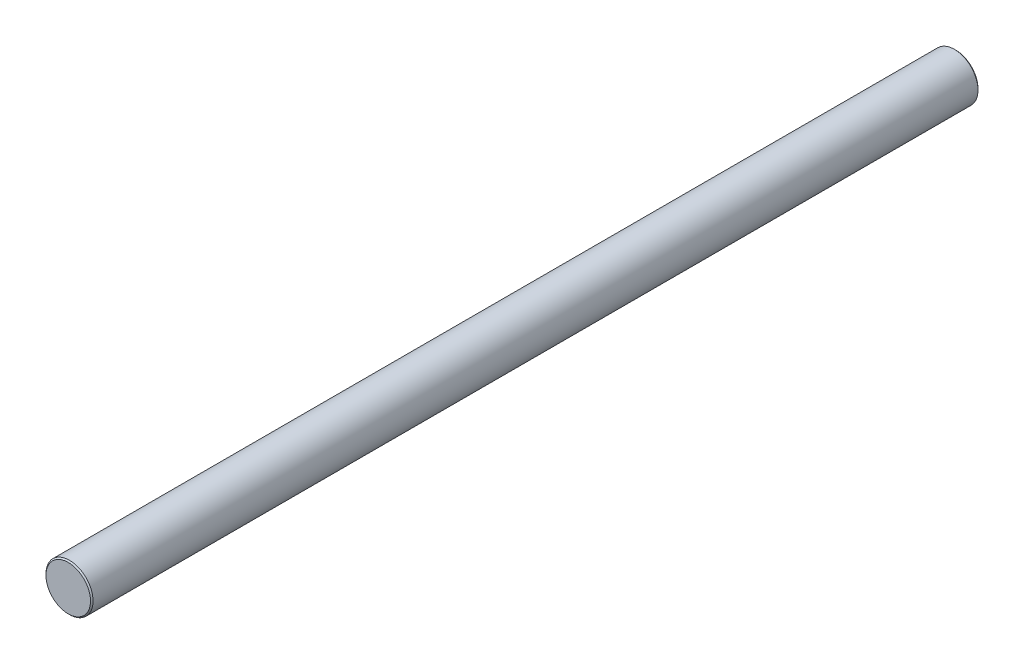
SolidWorks part; units mm, degrees
material "AISI 1045 Steel, cold drawn"
ref_plane "Front Plane" through (0, 0, 0) normal (0, 0, 1) x (1, 0, 0)
ref_plane "Top Plane" through (0, 0, 0) normal (0, 1, 0) x (1, 0, 0)
ref_plane "Right Plane" through (0, 0, 0) normal (1, 0, 0) x (0, 0, -1)
sketch "Sketch1" plane through (0, 0, 0) normal (0, 0, 1) x (1, 0, 0)
  circle A0 centre (0, 0) radius 4.7625
  dimension "D1" = 9.525
extrude "Boss-Extrude1" add sketch "Sketch1" along normal blind 179.5526
chamfer "Chamfer1" distance 0.254 angle 45 2 edges at (4.7625, 0, 179.5526) (4.7625, 0, 0)
